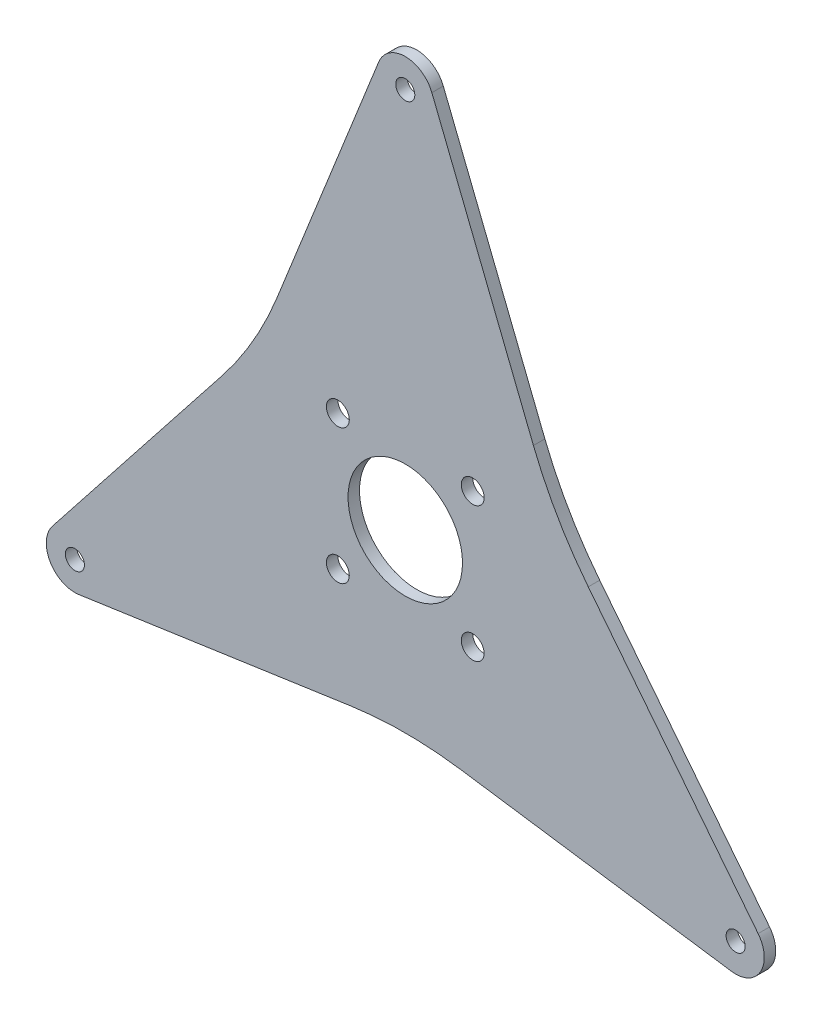
SolidWorks part; units mm, degrees
ref_plane "Front Plane" through (0, 0, 0) normal (0, 0, 1) x (1, 0, 0)
ref_plane "Top Plane" through (0, 0, 0) normal (0, 1, 0) x (1, 0, 0)
ref_plane "Right Plane" through (0, 0, 0) normal (1, 0, 0) x (0, 0, -1)
sketch "Sketch1" plane through (0, 0, 0) normal (0, 0, 1) x (1, 0, 0)
  line L0 (-35.3553, 35.3553) -> (0, 0) construction
  line L1 (0, 0) -> (0, 51.7411) construction
  line L2 (-184.9825, -90.7107) -> (-95.9322, 22.1916)
  line L3 (-67.1846, 71.9839) -> (-13.9335, 205.5549)
  line L4 (13.9335, 205.5549) -> (67.1846, 71.9839)
  line L5 (95.9322, 22.1916) -> (184.9825, -90.7107)
  line L6 (0, 0) -> (-81.3002, 46.9387) construction
  line L7 (-171.049, -114.8442) -> (-28.7476, -94.1755)
  line L8 (28.7476, -94.1755) -> (171.049, -114.8442)
  circle A0 centre (0, 200) radius 5
  circle A1 centre (173.2051, -100) radius 5
  circle A2 centre (-173.2051, -100) radius 5
  circle A3 centre (-35.3553, 35.3553) radius 6
  circle A4 centre (35.3553, 35.3553) radius 6
  circle A5 centre (35.3553, -35.3553) radius 6
  circle A6 centre (-35.3553, -35.3553) radius 6
  circle A7 centre (0, 0) radius 30
  arc A8 (13.9335, 205.5549) -> (-13.9335, 205.5549) centre (0, 200) ccw
  arc A9 (171.049, -114.8442) -> (184.9825, -90.7107) centre (173.2051, -100) ccw
  arc A10 (-184.9825, -90.7107) -> (-171.049, -114.8442) centre (-173.2051, -100) ccw
  arc A11 (67.1846, 71.9839) -> (95.9322, 22.1916) centre (252.9648, 146.0493) ccw
  arc A12 (-95.9322, 22.1916) -> (-67.1846, 71.9839) centre (-252.9648, 146.0493) ccw
  arc A13 (-28.7476, -94.1755) -> (28.7476, -94.1755) centre (0, -292.0986) cw
  circle A14 centre (0, 0) radius 67 construction
  point P10 (0, 0)
  point P21 (0, 0)
  point P30 (0, -90)
  point P40 (77.9423, 45)
  point P43 (-77.9423, 45)
  dimension "D1" = 10
  dimension "D4" = 50
  dimension "D6" = 12
  dimension "D8" = 60
  dimension "D9" = 30
  dimension "D11" = 200
  dimension "D12" = 200
  dimension "D2" = 200
  dimension "D5" = 45
  dimension "D10" = 60
  dimension "D13" = 90
  dimension "D14" = 90
  dimension "D3" = 3
  dimension "D7" = 4
extrude "Boss-Extrude1" add sketch "Sketch1" along normal blind 6
